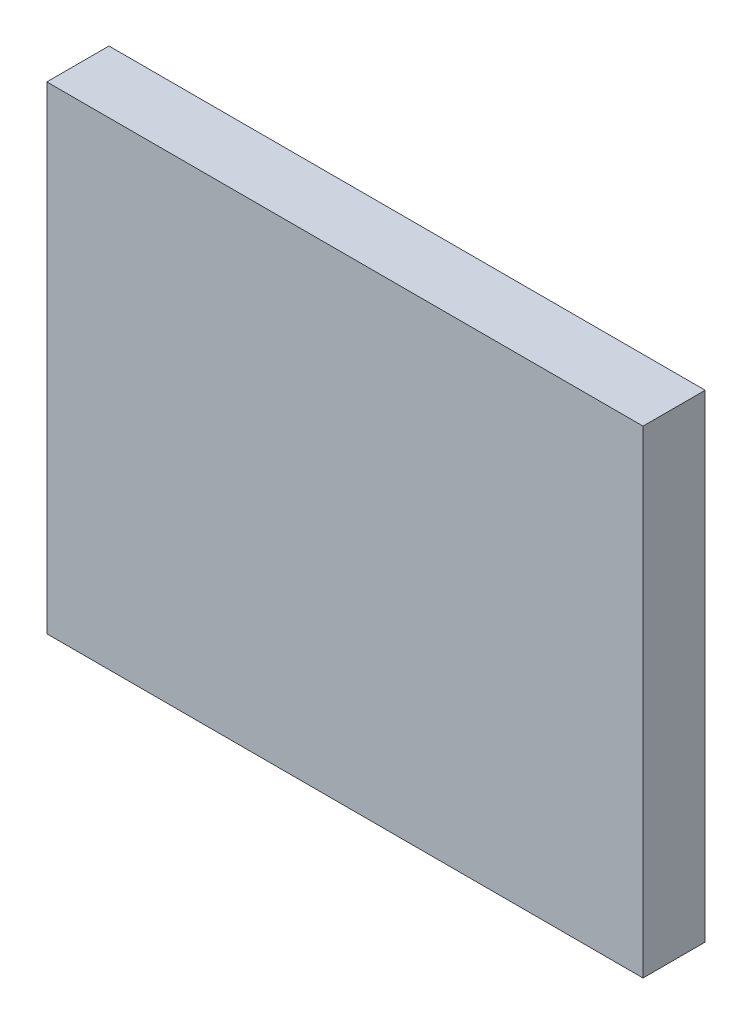
SolidWorks part; units mm, degrees
ref_plane "Front Plane" through (0, 0, 0) normal (0, 0, 1) x (1, 0, 0)
ref_plane "Top Plane" through (0, 0, 0) normal (0, 1, 0) x (1, 0, 0)
ref_plane "Right Plane" through (0, 0, 0) normal (1, 0, 0) x (0, 0, -1)
sketch "Sketch1" plane through (0, 0, 0) normal (0, 0, 1) x (1, 0, 0)
  line L1 (-46.4882, 38.4466) -> (49.43, 38.4466)
  line L2 (-46.4882, 38.4466) -> (-46.4882, -38.4466)
  line L3 (-46.4882, -38.4466) -> (49.43, -38.4466)
  line L4 (49.43, 38.4466) -> (49.43, -38.4466)
  line L5 (-46.4882, 38.4466) -> (49.43, -38.4466) construction
  line L6 (-46.4882, -38.4466) -> (49.43, 38.4466) construction
  point P0 (1.4709, 0)
extrude "Boss-Extrude1" add sketch "Sketch1" along normal blind 10
ref_point "Point1"
ref_axis "Axis1" through (1.4709, 0, 0) along (0, 0, 1)
